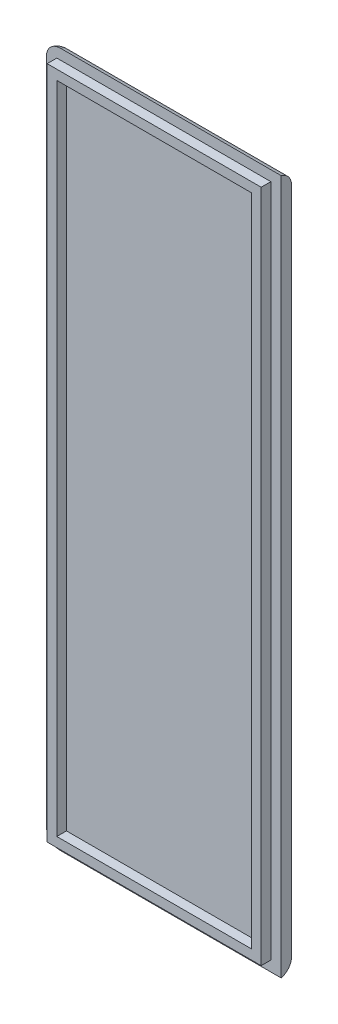
SolidWorks part; units mm, degrees
ref_plane "Plan de face" through (0, 0, 0) normal (0, 0, 1) x (1, 0, 0)
ref_plane "Plan de dessus" through (0, 0, 0) normal (0, 1, 0) x (1, 0, 0)
ref_plane "Plan de droite" through (0, 0, 0) normal (1, 0, 0) x (0, 0, -1)
sketch "Esquisse1" plane through (0, 0, 0) normal (0, 0, 1) x (1, 0, 0)
  line L1 (0, 0) -> (34, 0)
  line L2 (0, 0) -> (0, 100.65)
  line L3 (0, 100.65) -> (34, 100.65)
  line L4 (34, 0) -> (34, 100.65)
  dimension "D1" = 34
  dimension "D2" = 100.65
extrude "Boss.-Extru.1" add sketch "Esquisse1" along normal blind 1.5
sketch "Esquisse2" plane through (0, 0, 1.5) normal (0, 0, 1) x (1, 0, 0)
  line L0 (0, 0) -> (34, 0) construction
  line L1 (1.5, 99.15) -> (32.5, 99.15)
  line L2 (1.5, 99.15) -> (1.5, 1.5)
  line L3 (1.5, 1.5) -> (32.5, 1.5)
  line L4 (32.5, 99.15) -> (32.5, 1.5)
  line L5 (0, 100.65) -> (0, 0) construction
  line L6 (34, 0) -> (34, 100.65) construction
  line L7 (34, 100.65) -> (0, 100.65) construction
  line L9 (2.9, 97.75) -> (31.1, 97.75)
  line L10 (2.9, 97.75) -> (2.9, 2.9)
  line L11 (2.9, 2.9) -> (31.1, 2.9)
  line L12 (31.1, 97.75) -> (31.1, 2.9)
  dimension "D1" = 1.5
  dimension "D2" = 1.5
  dimension "D3" = 1.5
  dimension "D4" = 1.5
  dimension "D5" = 1.4
  dimension "D6" = 1.4
  dimension "D7" = 1.4
  dimension "D8" = 1.4
extrude "Boss.-Extru.2" add sketch "Esquisse2" along normal blind 1.4
fillet "Congé6" radius 2 1 edges at (0, 0, 0.75)
fillet "Congé8" radius 2 1 edges at (0, 100.65, 0.75)
fillet "Congé9" radius 2 5 edges at (18, 100.65, 0) (0.5858, 100.0642, 0) (0, 50.325, 0) (0.5858, 0.5858, 0) (18, 0, 0)
